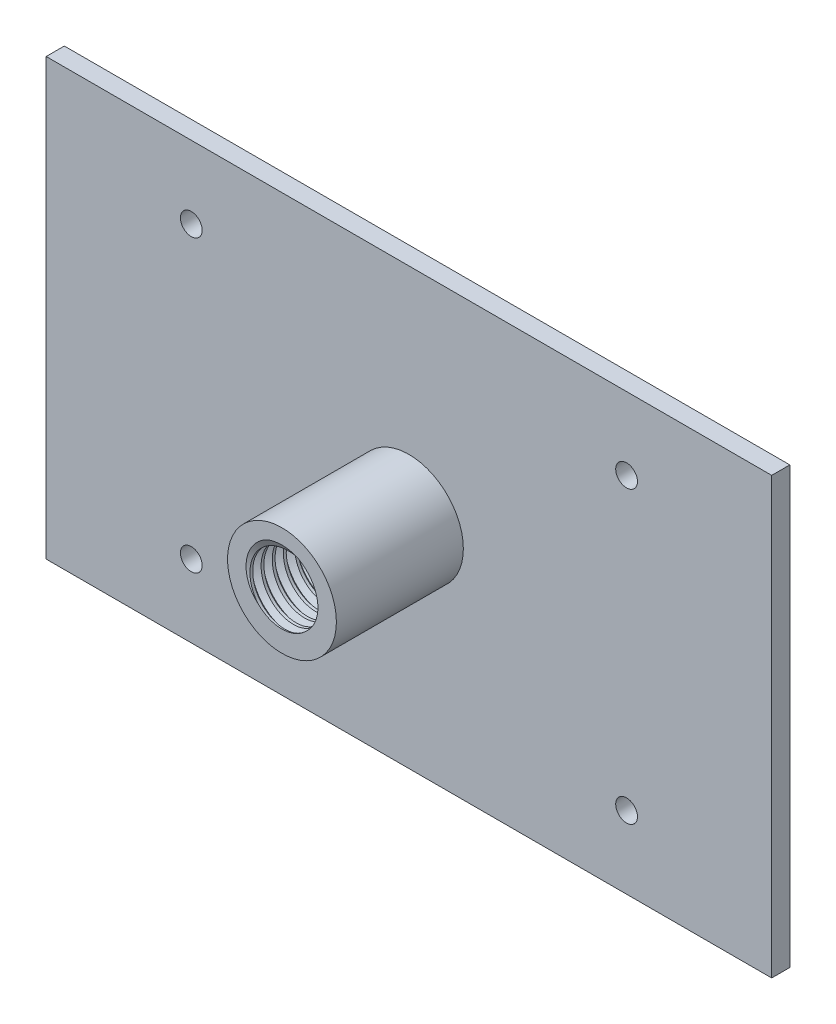
SolidWorks part; units mm, degrees
ref_plane "Front Plane" through (0, 0, 0) normal (0, 0, 1) x (1, 0, 0)
ref_plane "Top Plane" through (0, 0, 0) normal (0, 1, 0) x (1, 0, 0)
ref_plane "Right Plane" through (0, 0, 0) normal (1, 0, 0) x (0, 0, -1)
sketch "Sketch1" plane through (0, 0, 0) normal (0, 0, 1) x (1, 0, 0)
  line L1 (63.5, -38.1) -> (-63.5, -38.1)
  line L2 (63.5, -38.1) -> (63.5, 38.1)
  line L3 (63.5, 38.1) -> (-63.5, 38.1)
  line L4 (-63.5, -38.1) -> (-63.5, 38.1)
  line L5 (63.5, -38.1) -> (-63.5, 38.1) construction
  line L6 (63.5, 38.1) -> (-63.5, -38.1) construction
  point P0 (0, 0)
  dimension "D1" = 127
  dimension "D2" = 76.2
extrude "Boss-Extrude1" add sketch "Sketch1" along normal blind 3.175
sketch "Sketch2" plane through (0, 0, 3.175) normal (0, 0, 1) x (1, 0, 0)
  circle A0 centre (0, 0) radius 9.525
  dimension "D1" = 19.05
extrude "Boss-Extrude2" add sketch "Sketch2" along normal blind 25.4
hole_wizard "1/2-13 Tapped Hole3" positions "Sketch10" profile "Sketch11" tap size "1/2-13" standard "ANSI Inch" end condition through all
sketch "Sketch10" plane through (0, 0, 28.575) normal (0, 0, 1) x (1, 0, 0)
  point P0 (0, 0)
sketch "Sketch11" plane through (0, 0, 28.575) normal (1, 0, 0) x (0, -1, 0)
  line L0 (0, 0) -> (0, 28.575)
  line L1 (0, 28.575) -> (5.842, 28.575)
  line L2 (5.842, 28.575) -> (5.842, 0)
  line L5 (5.842, 0) -> (0, 0)
  line L11 (0, -6.35) -> (0, 107.95) construction
  dimension "Thru Tap Drill Dia." = 11.684
  dimension "Thru Tap Drill Depth" = 28.575
cosmetic thread "Hole Thread2" parameters "D2"=12.7
thread "Thread2" pitch 1.9538 method cut profile "Thread Profile2" start angle 0, offset 0, length 73.5, pitch 1.9538, diameter 11.684
ref_plane "Plane2" through (-5.842, 0, 28.575) normal (0, -1, 0) x (-1, 0, 0)
sketch "Thread Profile2" plane through (-5.842, 0, 28.575) normal (0, -1, 0) x (-1, 0, 0)
  line L0 (0, 0) -> (0, 1.9538) construction
  line L1 (0, 0) -> (1.0576, 0.6106)
  line L2 (1.0576, 0.6106) -> (1.0576, 0.8548)
  line L3 (1.0576, 0.8548) -> (0, 1.4654)
  line L4 (1.0576, 0.7327) -> (0, 0.7327) construction
  line L11 (0, 0) -> (0, 1.4654)
  point P2 (0, 0)
  dimension "Pitch" = 1.9538
  dimension "Profile_Angle" = 60
  dimension "Profile_Land" = 0.2442
  dimension "Profile_Height" = 1.0576
sketch "Sketch12" plane through (0, 0, 3.175) normal (0, 0, 1) x (1, 0, 0)
  line L0 (-38.1, 25.4) -> (-38.1, -25.4) construction
  line L1 (-38.1, 25.4) -> (38.1, 25.4) construction
  circle A0 centre (-38.1, 25.4) radius 1.905
  circle A1 centre (-38.1, -25.4) radius 1.905
  circle A2 centre (38.1, -25.4) radius 1.905
  circle A3 centre (38.1, 25.4) radius 1.905
  point P8 (-38.1, 0)
  point P9 (0, 25.4)
  dimension "D1" = 3.81
  dimension "D2" = 38.1
  dimension "D3" = 25.4
extrude "Cut-Extrude1" cut sketch "Sketch12" against normal through all
sketch "Sketch13" plane through (0, 0, 28.575) normal (0, 0, 1) x (1, 0, 0)
  circle A0 centre (0, 0) radius 9.525
extrude "Cut-Extrude2" cut sketch "Sketch13" against normal blind 3.175
sketch "Sketch14" plane through (0, 0, 0) normal (1, 0, 0) x (0, 0, -1)
  line L1 (-9.069, 51.1355) -> (14.1401, 51.1355)
  line L2 (-9.069, 51.1355) -> (-9.069, -43.9652)
  line L3 (-9.069, -43.9652) -> (14.1401, -43.9652)
  line L4 (14.1401, 51.1355) -> (14.1401, -43.9652)
extrude "Cut-Extrude3" [suppressed] cut sketch "Sketch14" against normal through all and the other way through all
